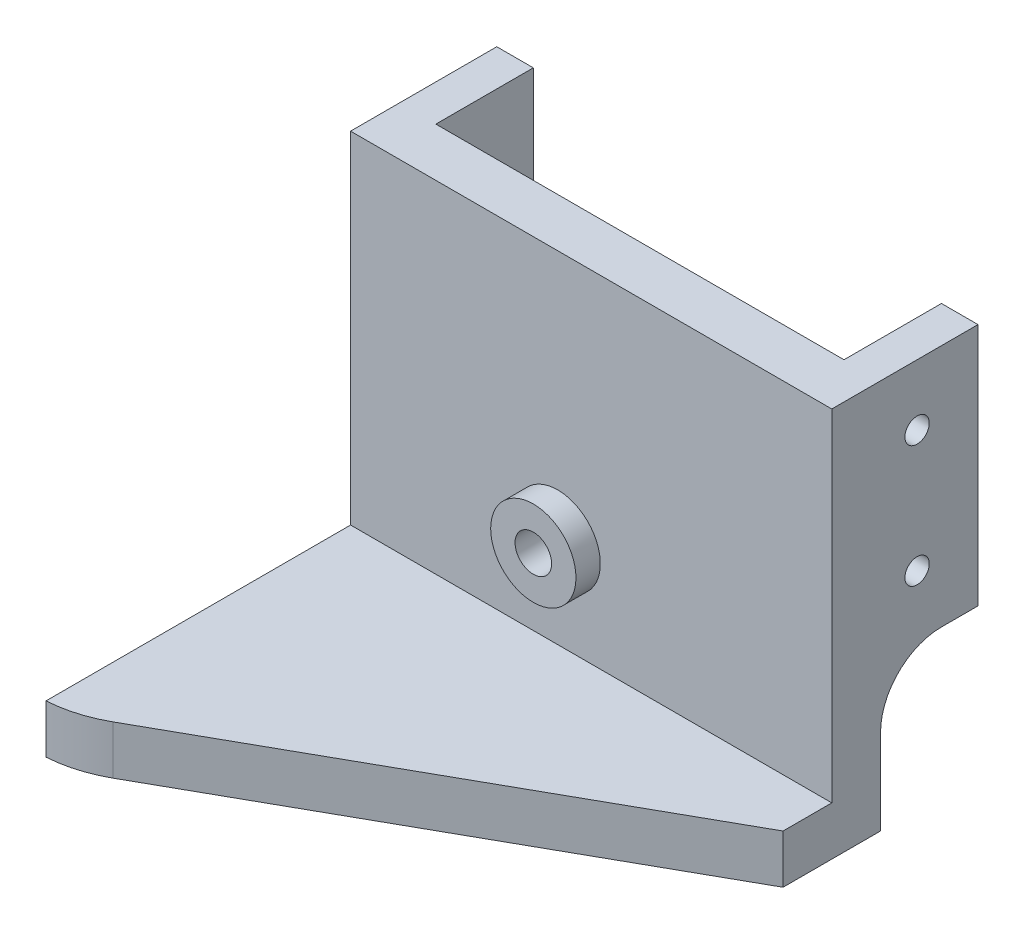
SolidWorks part; units mm, degrees
ref_plane "Front Plane" through (0, 0, 0) normal (0, 0, 1) x (1, 0, 0)
ref_plane "Top Plane" through (0, 0, 0) normal (0, 1, 0) x (1, 0, 0)
ref_plane "Right Plane" through (0, 0, 0) normal (1, 0, 0) x (0, 0, -1)
sketch "Sketch1" plane through (0, 0, 0) normal (0, 1, 0) x (1, 0, 0)
  line L1 (0, 0) -> (37.5, 0)
  line L2 (0, 0) -> (0, 12)
  line L3 (0, 12) -> (37.5, 12)
  line L4 (37.5, 0) -> (37.5, 12)
  line L5 (1, 12) -> (34.5, 12)
  line L6 (1, 12) -> (1, 4)
  line L7 (1, 4) -> (34.5, 4)
  line L8 (34.5, 12) -> (34.5, 4)
  dimension "D1" = 12
  dimension "D2" = 37.5
  dimension "D3" = 33.5
  dimension "D4" = 1
  dimension "10" = 8
extrude "Boss-Extrude1" add sketch "Sketch1" along normal blind 20 contours L3 L8 L7 L6 L2 L1 L4 region at (20.2225, 0, -3.0549)
sketch "Sketch2" plane through (0, 0, 0) normal (0, -1, 0) x (1, 0, 0)
  line L0 (37.5, 0) -> (37.5, -12) construction
  line L1 (0, 0) -> (37.5, 0)
  line L2 (0, 0) -> (0, -4)
  line L3 (0, -4) -> (37.5, -4)
  line L4 (37.5, 0) -> (37.5, -4)
extrude "Boss-Extrude2" add sketch "Sketch2" along normal blind 12
fillet "Fillet1" radius 5 2 edges at (0.5, 0, -4) (36, 0, -4)
sketch "Sketch3" plane through (0, 0, 0) normal (0, 0, 1) x (1, 0, 0)
  line L0 (37.5, 20) -> (37.5, -12) construction
  line L1 (0, -12) -> (37.5, -12)
  line L2 (0, -12) -> (0, -8)
  line L3 (0, -8) -> (37.5, -8)
  line L4 (37.5, -12) -> (37.5, -8)
  dimension "D1" = 4
extrude "Boss-Extrude3" add sketch "Sketch3" along normal blind 25 contours L3 L4 L1 L2
sketch "Sketch4" plane through (0, 0, 0) normal (0, 0, 1) x (1, 0, 0)
  line L0 (0, -8) -> (37.5, -8) construction
  line L1 (0, 20) -> (0, -8) construction
  circle A0 centre (15, -0.5) radius 1.5
  circle A1 centre (15, -0.5) radius 3.5
  dimension "D1" = 3
  dimension "D2" = 7.5
  dimension "D4" = 15
  dimension "D3" = 2
extrude "Boss-Extrude4" add sketch "Sketch4" along normal blind 2
sketch "Sketch5" plane through (0, 0, 2) normal (0, 0, 1) x (1, 0, 0)
  circle A0 centre (15, -0.5) radius 1.5 construction
  circle A1 centre (15, -0.5) radius 1.5
extrude "Cut-Extrude1" cut sketch "Sketch5" against normal through all contours A1
sketch "Sketch6" plane through (0, -8, 0) normal (0, 1, 0) x (1, 0, 0)
  line L0 (0, -25) -> (37.5, -4)
  line L1 (37.5, -25) -> (37.5, 0) construction
  line L2 (37.5, -4) -> (37.5, -25)
  line L3 (37.5, -25) -> (0, -25)
  dimension "D1" = 4
extrude "Cut-Extrude2" cut sketch "Sketch6" against normal blind 10
sketch "Sketch7" plane through (0, 0, 0) normal (-1, 0, 0) x (0, 0, 1)
  line L0 (-12, 20) -> (-12, 0) construction
  line L1 (0, 20) -> (-12, 20) construction
  line L2 (-9, 0) -> (-12, 0) construction
  circle A0 centre (-7, 15) radius 1
  circle A1 centre (-7, 5) radius 1
  dimension "D1" = 2
  dimension "D3" = 5
  dimension "D2" = 5
  dimension "D4" = 10
  dimension "D5" = 5
extrude "Cut-Extrude3" cut sketch "Sketch7" against normal through all both and the other way through all
sketch "Sketch8" plane through (0, 0, 0) normal (-1, 0, 0) x (0, 0, 1)
  line L8 (-12, 0) -> (-9, 0)
  line L9 (-4, -5) -> (-4, -12)
  line L10 (-4, -12) -> (25, -12)
  line L11 (25, -12) -> (25, -8)
  line L12 (25, -8) -> (0, -8)
  line L13 (0, -8) -> (0, 20)
  line L14 (0, 20) -> (-12, 20)
  line L15 (-12, 20) -> (-12, 0)
  line L16 (-12, 0) -> (-9, 0)
  line L17 (-4, -5) -> (-4, -12)
  line L18 (-4, -12) -> (25, -12)
  line L19 (25, -12) -> (25, -8)
  line L20 (25, -8) -> (0, -8)
  line L21 (0, -8) -> (0, 20)
  line L22 (0, 20) -> (-12, 20)
  line L23 (-12, 20) -> (-12, 0)
  circle A0 centre (-7, 15) radius 1 construction
  arc A1 (-4, -5) -> (-9, 0) centre (-9, -5) ccw
  arc A2 (-4, -5) -> (-9, 0) centre (-9, -5) ccw
  circle A3 centre (-7, 15) radius 1
  circle A4 centre (-7, 5) radius 1 construction
  circle A5 centre (-7, 5) radius 1
  circle A6 centre (-7, 5) radius 3
  circle A7 centre (-7, 15) radius 3
  line M12 (-12, 0) -> (-9, 0)
  arc M13 (-9, 0) -> (-4, -5) centre (-9, -5) cw
  line M14 (-4, -5) -> (-4, -12)
  line M15 (-4, -12) -> (25, -12)
  line M16 (25, -12) -> (25, -8)
  line M17 (25, -8) -> (0, -8)
  line M18 (0, -8) -> (0, 20)
  line M19 (0, 20) -> (-12, 20)
  line M20 (-12, 20) -> (-12, 0)
  dimension "D1" = 0
  dimension "D2" = 2
extrude "Boss-Extrude5" add sketch "Sketch8" along normal blind 2 contours A7 A6 M20 M12 M13 M14 M15 M16 M17 M18 M19 region at (0, 10, -11.5108)
fillet "Fillet2" radius 10 1 edges at (0, -10, 25)
